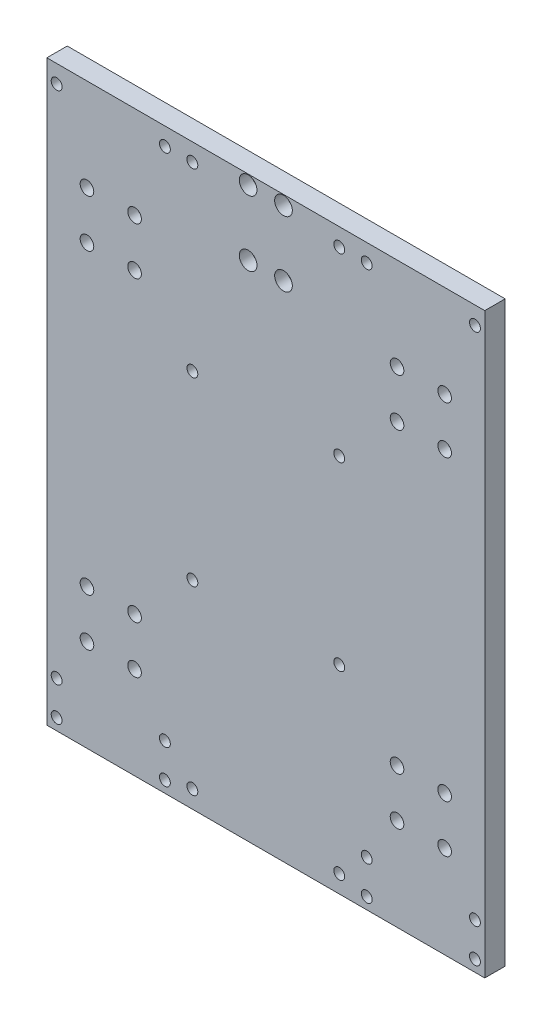
SolidWorks part; units mm, degrees
ref_plane "Płaszczyzna przednia" through (0, 0, 0) normal (0, 0, 1) x (1, 0, 0)
ref_plane "Płaszczyzna górna" through (0, 0, 0) normal (0, 1, 0) x (1, 0, 0)
ref_plane "Płaszczyzna prawa" through (0, 0, 0) normal (1, 0, 0) x (0, 0, -1)
sketch "Szkic1" plane through (0, 0, 0) normal (0, 0, 1) x (1, 0, 0)
  line L1 (161, -212.5) -> (-161, -212.5)
  line L2 (161, -212.5) -> (161, 212.5)
  line L3 (161, 212.5) -> (-161, 212.5)
  line L4 (-161, -212.5) -> (-161, 212.5)
  line L5 (161, -212.5) -> (-161, 212.5) construction
  line L6 (161, 212.5) -> (-161, -212.5) construction
  point P0 (0, 0)
  dimension "D1" = 322
  dimension "D2" = 425
extrude "Dodanie-wyciągnięcie1" add sketch "Szkic1" along normal blind 15
sketch "Szkic2" plane through (0, 0, 15) normal (0, 0, 1) x (1, 0, 0)
  line L0 (161, 212.5) -> (-161, 212.5) construction
  line L1 (-161, 212.5) -> (-161, -212.5) construction
  circle A0 centre (-131.5, 144.5) radius 3
  dimension "D1" = 68
  dimension "D3" = 6
  dimension "D2" = 29.5
extrude "Wytnij-wyciągnięcie1" cut sketch "Szkic2" against normal blind 15
sketch "Szkic3" plane through (0, 0, 15) normal (0, 0, 1) x (1, 0, 0)
  circle A0 centre (-131.5, 144.5) radius 5
  dimension "D1" = 10
extrude "Wytnij-wyciągnięcie2" cut sketch "Szkic3" against normal blind 7
pattern_linear "Szyk liniowy1" count 2 spacing 35 along (1, 0, 0) count 2 spacing 35 along (0, -1, 0) of "Wytnij-wyciągnięcie1", "Wytnij-wyciągnięcie2"
pattern_linear "Szyk liniowy2" count 2 spacing 228 along (1, 0, 0) count 2 spacing 254 along (0, -1, 0) of "Szyk liniowy1"
sketch "Szkic6" plane through (0, 0, 15) normal (0, 0, 1) x (1, 0, 0)
  line L0 (-161, 212.5) -> (-161, -212.5) construction
  line L1 (161, 212.5) -> (-161, 212.5) construction
  circle A0 centre (-153.8, 199.5) radius 4
  circle A1 centre (-74.2, 199.5) radius 4
  dimension "D1" = 8
  dimension "D2" = 8
  dimension "D3" = 7.2
  dimension "D4" = 13
  dimension "D5" = 79.6
extrude "Wytnij-wyciągnięcie3" cut sketch "Szkic6" against normal blind 20
sketch "Szkic7" plane through (0, 0, 15) normal (0, 0, 1) x (1, 0, 0)
  line L0 (-161, 212.5) -> (-161, -212.5) construction
  line L1 (-161, -212.5) -> (161, -212.5) construction
  circle A0 centre (-153.8, -204) radius 4
  circle A1 centre (-153.8, -179) radius 4
  circle A2 centre (-74.2, -204) radius 4
  circle A3 centre (-74.2, -179) radius 4
  dimension "D1" = 8
  dimension "D2" = 8
  dimension "D3" = 8
  dimension "D4" = 8
  dimension "D5" = 7.2
  dimension "D6" = 8.5
  dimension "D7" = 25
  dimension "D8" = 79.6
extrude "Wytnij-wyciągnięcie4" cut sketch "Szkic7" against normal blind 20
sketch "Szkic10" plane through (0, 0, 15) normal (0, 0, 1) x (1, 0, 0)
  line L0 (161, 212.5) -> (-161, 212.5) construction
  line L1 (161, -212.5) -> (161, 212.5) construction
  circle A0 centre (74.2, 199.5) radius 4
  circle A1 centre (153.8, 199.5) radius 4
  dimension "D1" = 8
  dimension "D2" = 8
  dimension "D3" = 79.6
  dimension "D4" = 13
  dimension "D5" = 7.2
extrude "Wytnij-wyciągnięcie5" cut sketch "Szkic10" against normal blind 21
sketch "Szkic11" plane through (0, 0, 15) normal (0, 0, 1) x (1, 0, 0)
  line L0 (161, -212.5) -> (161, 212.5) construction
  line L2 (-161, -212.5) -> (161, -212.5) construction
  circle A0 centre (153.8, -179) radius 4
  circle A1 centre (153.8, -204) radius 4
  circle A2 centre (74.2, -204) radius 4
  circle A3 centre (74.2, -179) radius 4
  dimension "D1" = 7.2
  dimension "D5" = 8
  dimension "D6" = 8
  dimension "D7" = 8
  dimension "D8" = 8
  dimension "D2" = 8.5
  dimension "D3" = 25
  dimension "D4" = 79.6
extrude "Wytnij-wyciągnięcie6" cut sketch "Szkic11" against normal blind 21
sketch "Szkic12" plane through (0, 0, 15) normal (0, 0, 1) x (1, 0, 0)
  line L0 (161, 212.5) -> (-161, 212.5) construction
  circle A0 centre (-13, 205.5) radius 4
  circle A1 centre (-74.2, 199.5) radius 4 construction
  circle A2 centre (13, 205.5) radius 4
  circle A3 centre (-13, 157.5) radius 4
  circle A4 centre (13, 157.5) radius 4
  dimension "D1" = 7
  dimension "D3" = 26
  dimension "D4" = 48
  dimension "D5" = 8
  dimension "D6" = 8
  dimension "D7" = 8
  dimension "D8" = 8
  dimension "D2" = 61.2
extrude "Wytnij-wyciągnięcie7" cut sketch "Szkic12" against normal blind 15
sketch "Szkic13" plane through (0, 0, 15) normal (0, 0, 1) x (1, 0, 0)
  circle A0 centre (-13, 205.5) radius 6.5
  circle A1 centre (13, 205.5) radius 6.5
  circle A2 centre (13, 157.5) radius 6.5
  circle A3 centre (-13, 157.5) radius 6.5
  dimension "D1" = 13
  dimension "D2" = 13
  dimension "D3" = 13
  dimension "D4" = 13
extrude "Wytnij-wyciągnięcie8" cut sketch "Szkic13" against normal blind 9
sketch "Szkic14" plane through (0, 0, 15) normal (0, 0, 1) x (1, 0, 0)
  line L0 (161, 212.5) -> (-161, 212.5) construction
  line L1 (-161, 212.5) -> (-161, -212.5) construction
  circle A0 centre (-54, 199.5) radius 4
  circle A1 centre (54, 199.5) radius 4
  dimension "D1" = 13
  dimension "D4" = 8
  dimension "D5" = 8
  dimension "D2" = 107
  dimension "D3" = 108
extrude "Wytnij-wyciągnięcie9" cut sketch "Szkic14" against normal blind 15
pattern_linear "Szyk liniowy3" count 4 spacing 133 along (0, -1, 0) of "Wytnij-wyciągnięcie9"
